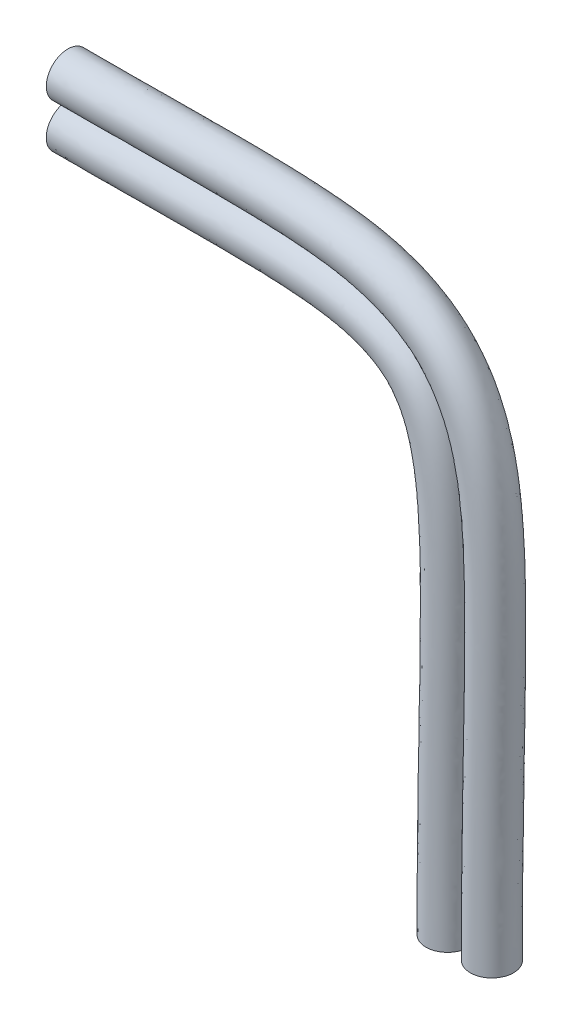
SolidWorks part; units mm, degrees
ref_plane "Front Plane" through (0, 0, 0) normal (0, 0, 1) x (1, 0, 0)
ref_plane "Top Plane" through (0, 0, 0) normal (0, 1, 0) x (1, 0, 0)
ref_plane "Right Plane" through (0, 0, 0) normal (1, 0, 0) x (0, 0, -1)
sketch "Sketch1" plane through (0, 0, 0) normal (0, 1, 0) x (1, 0, 0)
  circle A0 centre (2.0059, 0) radius 0.75
  circle A1 centre (3.5444, 0) radius 0.75
  dimension "D1" = 1.5
  dimension "D2" = 1.5
sketch "Sketch2" plane through (0, 0, 0) normal (0, 0, 1) x (1, 0, 0)
  line L0 (2.7559, 0) -> (1.2559, 0) construction
  line L1 (2.0059, 1.5299) -> (2.0059, -1.5862) construction
  line L2 (-22.85, 17.7399) -> (-3.2673, 17.7399) construction
  spline S0 degree 3 poles (2.0059, 0) (2.0059, 19.1583) (4.239, 17.7399) (-11.1672, 17.7399) knots 0 0 0 0 1 1 1 1
sweep "Sweep1" add profiles "Sketch1" path "Sketch2"
